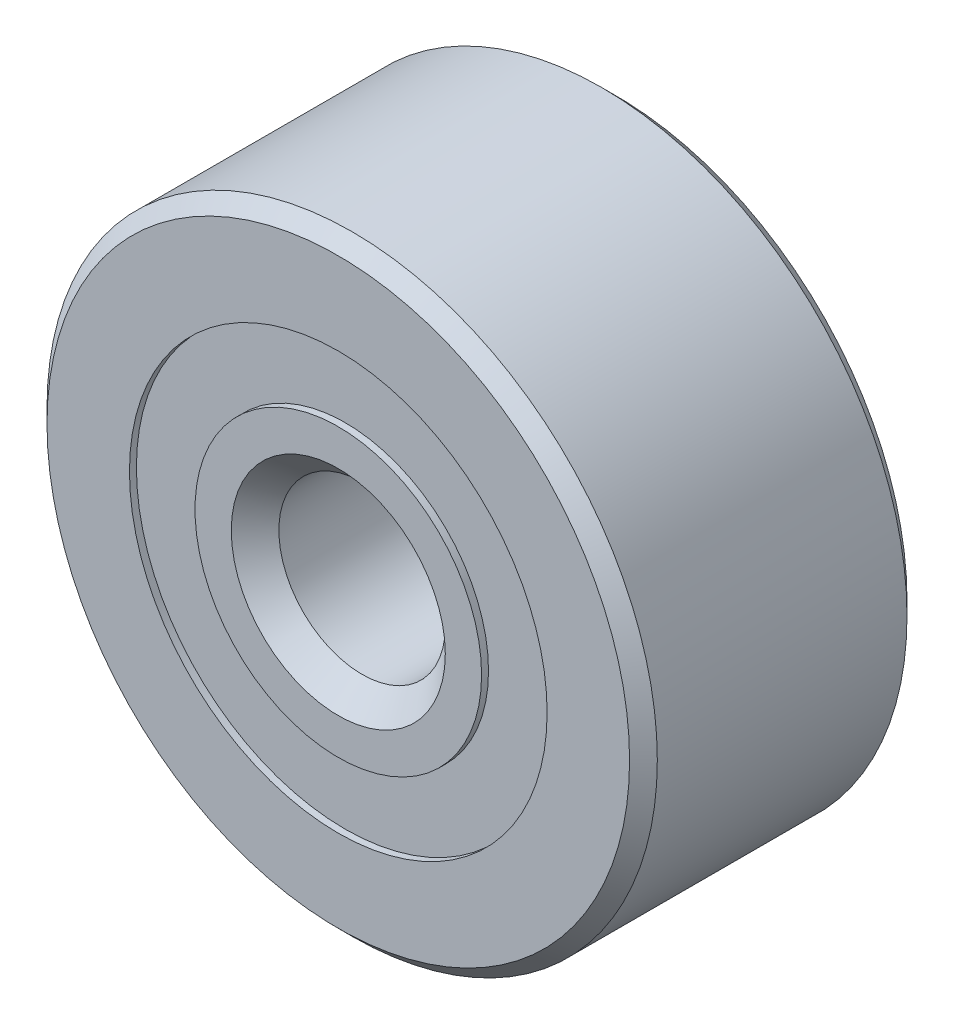
SolidWorks part; units mm, degrees
ref_plane "Front Plane" through (0, 0, 0) normal (0, 0, 1) x (1, 0, 0)
ref_plane "Top Plane" through (0, 0, 0) normal (0, 1, 0) x (1, 0, 0)
ref_plane "Right Plane" through (0, 0, 0) normal (1, 0, 0) x (0, 0, -1)
sketch "Sketch1" plane through (0, 0, 0) normal (1, 0, 0) x (0, 0, -1)
  line L0 (-3.9688, 0) -> (3.9688, 0) construction
  line L1 (0, 8.7312) -> (0, -8.7312) construction
  line L2 (3.5719, 8.7313) -> (-3.5719, 8.7312)
  line L3 (-3.5719, 8.7312) -> (-3.9688, 8.3344)
  line L4 (-3.9688, 8.3344) -> (-3.9688, 5.9749)
  line L5 (-3.9688, 5.9749) -> (-1.7639, 5.9749)
  line L6 (3.9688, 5.9749) -> (1.7639, 5.9749)
  line L7 (3.9688, 8.3344) -> (3.9688, 5.9749)
  line L8 (3.5719, 8.7313) -> (3.9688, 8.3344)
  line L9 (0, 8.7312) -> (0, 5.5562) construction
  line L10 (0, 5.5562) -> (0, 2.3813) construction
  arc A0 (-1.7639, 5.9749) -> (1.7639, 5.9749) centre (0, 5.5562) cw
  point P14 (0, 2.3813)
  dimension "Width" = 7.9375
  dimension "OD" = 17.4625
  dimension "D1" = 45
  dimension "D2" = 0.3969
  dimension "D3" = 3.5278
  dimension "D4" = 0.4187
revolve "Revolve1" add sketch "Sketch1" angle 360 about L0
sketch "Sketch2" plane through (0, 0, 0) normal (1, 0, 0) x (0, 0, -1)
  line L0 (-3.7703, 5.1376) -> (-1.7639, 5.1376)
  line L1 (-3.9688, 8.3344) -> (-3.9688, -8.3344) construction
  line L2 (-3.9688, 4.0999) -> (-3.7703, 4.0999) construction
  line L3 (-3.7703, 3.9015) -> (-2.9311, 3.0623)
  line L4 (-2.9311, 3.0623) -> (0, 3.0623)
  line L5 (0, 8.7312) -> (0, -8.7312) construction
  line L6 (0, 3.0623) -> (0, 3.7434)
  line L7 (0, 3.7434) -> (0, 2.3813) construction
  line L8 (-3.9688, 5.1376) -> (-3.9688, 3.0623) construction
  line L9 (-3.9688, 3.0623) -> (-2.9311, 3.0623) construction
  line L10 (-3.7703, 5.1376) -> (-3.7703, 3.9015)
  line L11 (-3.7703, 5.1376) -> (-3.7703, 8.5328) construction
  line L12 (-3.5719, 8.7312) -> (-3.9688, 8.3344) construction
  arc A0 (-1.7639, 5.1376) -> (0, 3.7434) centre (0, 5.5562) ccw
  arc A1 (1.7639, 5.9749) -> (-1.7639, 5.9749) centre (0, 5.5562) ccw construction
  circle A2 centre (0, 5.5562) radius 1.8129 construction
  dimension "D1" = 45
revolve "Revolve2" [suppressed] add sketch "Sketch2" angle 360 about L0
sketch "Sketch3" plane through (0, 0, 0) normal (1, 0, 0) x (0, 0, -1)
  line L0 (-3.7703, 3.9015) -> (-2.9311, 3.0623)
  line L1 (-2.9311, 3.0623) -> (0, 3.0623)
  line L2 (0, 3.0623) -> (0, 3.7434)
  line L3 (-3.9688, 4.0999) -> (-3.9688, 3.0623)
  line L4 (-3.9688, 5.1376) -> (-3.9688, 3.0623) construction
  line L5 (-3.9688, 3.0623) -> (-3.2877, 2.3813)
  line L6 (-3.2877, 2.3813) -> (3.5719, 2.3812)
  line L7 (3.5719, 8.7313) -> (3.5719, -8.7313) construction
  line L8 (3.5719, 2.3812) -> (3.9688, 2.7781)
  line L9 (3.9688, -8.3344) -> (3.9688, 8.3344) construction
  line L10 (3.9688, 2.7781) -> (3.9688, 5.1376)
  line L11 (3.9688, 5.1376) -> (1.7639, 5.1376)
  line L12 (-3.9688, 4.0999) -> (-3.7703, 4.0999)
  line L13 (3.5719, 8.7313) -> (3.9688, 8.3344) construction
  line L14 (-3.7703, 4.0999) -> (-3.7703, 3.9015)
  circle A0 centre (0, 5.5562) radius 1.8129 construction
  arc A1 (1.7639, 5.1376) -> (0, 3.7434) centre (0, 5.5562) cw
revolve "Revolve3" add sketch "Sketch3" angle 360 about L0
sketch "Sketch4" plane through (0, 0, 0) normal (1, 0, 0) x (0, 0, -1)
  line L0 (-1.8129, 5.5562) -> (1.8129, 5.5562)
  circle A1 centre (0, 5.5562) radius 1.8129 construction
  arc A2 (-1.8129, 5.5562) -> (1.8129, 5.5562) centre (0, 5.5562) cw
  arc A3 (1.7639, 5.9749) -> (-1.7639, 5.9749) centre (0, 5.5562) ccw construction
revolve "Revolve4" add sketch "Sketch4" angle 360 about L0
ref_axis "Axis1" through (0, 0, -3.9688) along (0, 0, 1)
pattern_circular "CirPattern1" count 8 every 45 about axis through (0, 0, -3.9688) along (0, 0, 1) of bodies 104
sketch "Sketch5" plane through (0, 0, 0) normal (1, 0, 0) x (0, 0, -1)
  line L0 (-3.9688, 5.9749) -> (-1.7639, 5.9749) construction
  line L1 (-3.7703, 5.9749) -> (-1.8129, 5.9749)
  line L2 (-3.7703, 5.9749) -> (-3.7703, 4.0999)
  line L3 (-3.7703, 4.0999) -> (-1.8129, 4.0999)
  line L4 (-1.8129, 5.9749) -> (-1.8129, 4.0999)
  line L6 (-3.5719, 8.7312) -> (-3.9688, 8.3344) construction
  line L7 (0, 8.7312) -> (0, 2.3813) construction
  line L8 (3.7703, 4.0999) -> (1.8129, 4.0999)
  line L9 (1.8129, 5.9749) -> (1.8129, 4.0999)
  line L10 (3.7703, 5.9749) -> (1.8129, 5.9749)
  line L11 (3.7703, 5.9749) -> (3.7703, 4.0999)
  circle A0 centre (0, 5.5562) radius 1.8129 construction
  point P10 (-3.7703, 8.5328)
revolve "Revolve5" add sketch "Sketch5" angle 360 about L0
equation "\"D2@Sketch1\" = \"Width@Sketch1\"*.05"
equation "\"D3@Sketch1\" = \"Width@Sketch1\"/2.25"
equation "\"D4@Sketch1\" = (((\"OD@Sketch1\"-\"Width@Sketch1\")/2)/3.25)/3.5"
equation "\"D2@CirPattern1\" = 360/\"Balls@CirPattern1\""
